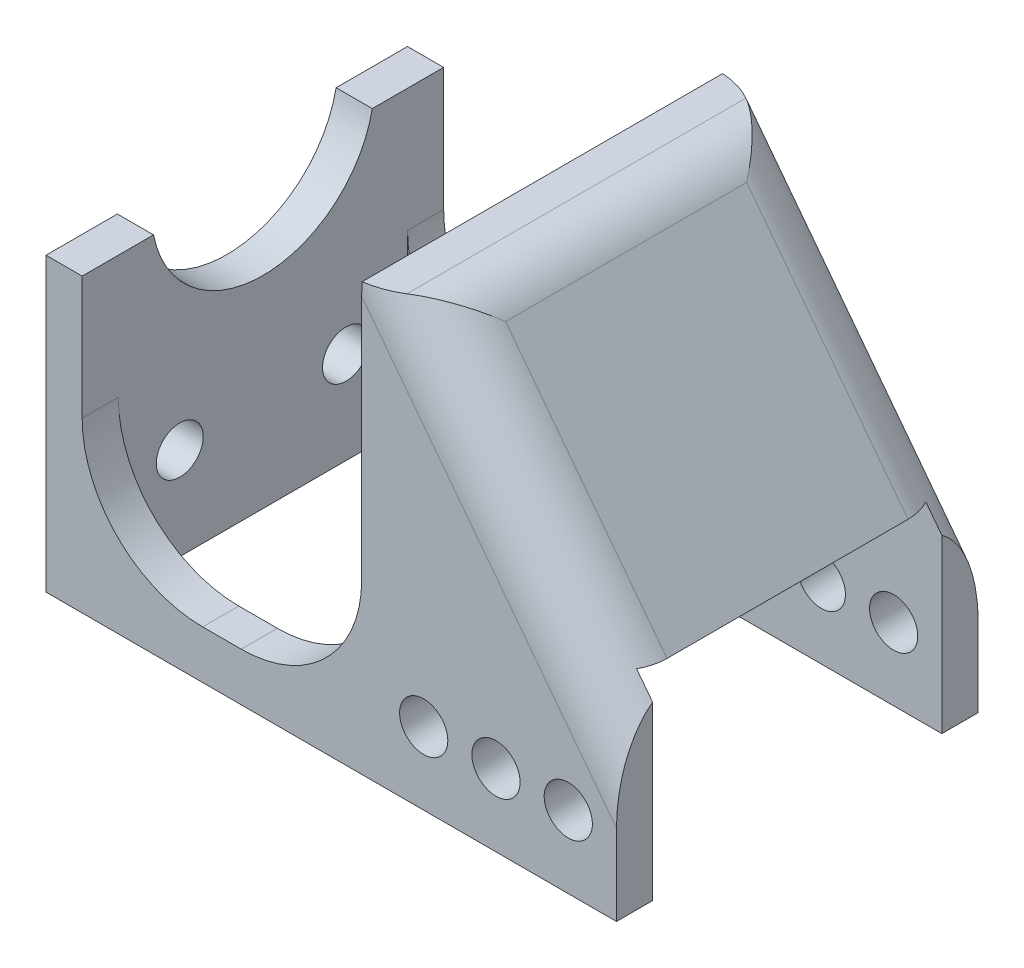
SolidWorks part; units mm, degrees
ref_plane "Front Plane" through (0, 0, 0) normal (0, 0, 1) x (1, 0, 0)
ref_plane "Top Plane" through (0, 0, 0) normal (0, 1, 0) x (1, 0, 0)
ref_plane "Right Plane" through (0, 0, 0) normal (1, 0, 0) x (0, 0, -1)
sketch "Sketch1" plane through (0, 0, 0) normal (0, 0, 1) x (1, 0, 0)
  line L0 (0, 0) -> (-10, -13.0323) construction
  line L1 (0, 0) -> (10, -13.0323) construction
  line L2 (-10, -13.0323) -> (10, -13.0323)
  line L9 (-11.1437, 22.3593) -> (-5.7608, 22.5296)
  line L10 (-11.1437, -9.0323) -> (-11.1437, 22.3593)
  line L11 (10, 1.9125) -> (10, -13.0323)
  line L12 (-5.7608, 22.5296) -> (10, 1.9125)
  line L13 (-10, -13.0323) -> (-37.3437, -13.0323)
  line L14 (-37.3437, -13.0323) -> (-37.3437, 11.1805)
  line L15 (-37.3437, 11.1805) -> (-34.3437, 11.1805)
  line L16 (-34.3437, 11.1805) -> (-34.3437, -9.0323)
  line L17 (-11.1437, -9.0323) -> (-34.3437, -9.0323)
  circle A2 centre (0, -7.0323) radius 2
  circle A3 centre (6, -7.0323) radius 2
  circle A4 centre (-6, -7.0323) radius 2
  point P3 (0, 0)
  dimension "D6" = 4
  dimension "D7" = 4
  dimension "D10" = 4
  dimension "D1" = 75
  dimension "D2" = 20
  dimension "D3" = 35.41
  dimension "D4" = 23.2
  dimension "D5" = 6
  dimension "D8" = 6
  dimension "D9" = 6
  dimension "D11" = 3
  dimension "D12" = 4
extrude "Boss-Extrude1" add sketch "Sketch1" along normal blind 30
sketch "Sketch2" plane through (10, 0, 0) normal (1, 0, 0) x (0, 0, -1)
  line L1 (-27, -13.0323) -> (-3, -13.0323)
  line L2 (-27, -13.0323) -> (-27, 2.9677)
  line L3 (-27, 2.9677) -> (-3, 2.9677)
  line L4 (-3, -13.0323) -> (-3, 2.9677)
  line L5 (-30, -13.0323) -> (0, -13.0323) construction
  dimension "D1" = 16
extrude "Cut-Extrude1" cut sketch "Sketch2" against normal up to surface (44.3437 mm away) up to face at (-34.3437, 1.0741, 15)
sketch "Sketch3" plane through (-11.1437, 0, 0) normal (-1, 0, 0) x (0, 0, 1)
  line L0 (3, 2.9677) -> (27, 2.9677) construction
  circle A0 centre (15, 12.9677) radius 9
  circle A1 centre (15, 12.9677) radius 6 construction
  circle A2 centre (15, 18.9677) radius 2
  circle A3 centre (15, 6.9677) radius 2
  circle A4 centre (9, 12.9677) radius 2
  circle A5 centre (21, 12.9677) radius 2
  point P5 (15, 2.9677)
  dimension "D1" = 18
  dimension "D2" = 10
  dimension "D3" = 12
  dimension "D4" = 4
  dimension "D5" = 4
  dimension "D6" = 4
  dimension "D7" = 4
extrude "Cut-Extrude2" cut sketch "Sketch3" against normal blind 3
fillet "Fillet1" [suppressed] radius 2
sketch "Sketch4" plane through (-34.3437, 0, 0) normal (1, 0, 0) x (0, 0, -1)
  circle A0 centre (-15, 12.9677) radius 2 construction
  arc A1 (-16.9663, 12.6021) -> (-13.0337, 13.3334) centre (-15, 12.9677) ccw construction
  arc A2 (-16.9663, 12.6021) -> (-13.0337, 13.3334) centre (-15, 12.9677) ccw construction
  circle A3 centre (-15, 12.9677) radius 9.25
  dimension "D1" = 4
  dimension "D2" = 18.5
extrude "Cut-Extrude3" cut sketch "Sketch4" against normal through all
fillet "Fillet2" radius 10 4 edges at (-11.1437, -9.0323, 1.5) (-11.1437, -9.0323, 28.5) (-34.3437, -9.0323, 28.5) (-34.3437, -9.0323, 1.5)
fillet "Fillet3" radius 5 3 edges at (-5.7608, 22.5296, 15) (2.1196, 12.2211, 30) (2.1196, 12.2211, 0)
hole_wizard "M3.5 Clearance Hole1" positions "Sketch5" profile "Sketch6" hole size "M3.5" standard "ANSI Metric" end condition through all
sketch "Sketch5" plane through (-37.3437, 0, 0) normal (-1, 0, 0) x (0, 0, 1)
  point P0 (8.1, -5.3723)
  point P3 (21.9, -5.3723)
sketch "Sketch6" plane through (-37.3437, -5.3723, 8.1) normal (0, 1, 0) x (0, 0, 1)
  line L0 (0, 0) -> (0, 47.3437)
  line L1 (0, 47.3437) -> (1.95, 47.3437)
  line L2 (1.95, 47.3437) -> (1.95, 0.025)
  line L3 (1.95, 0.025) -> (1.975, 0)
  line L5 (1.975, 0) -> (0, 0)
  line L6 (-1.95, 0.025) -> (-1.975, 0) construction
  line L11 (0, -6.35) -> (0, 107.95) construction
  dimension "Thru Hole Dia." = 3.9
  dimension "Thru Hole Depth" = 47.3437
  dimension "Near C'Sink Dia." = 3.95
  dimension "Near C'Sink Angle" = 90
